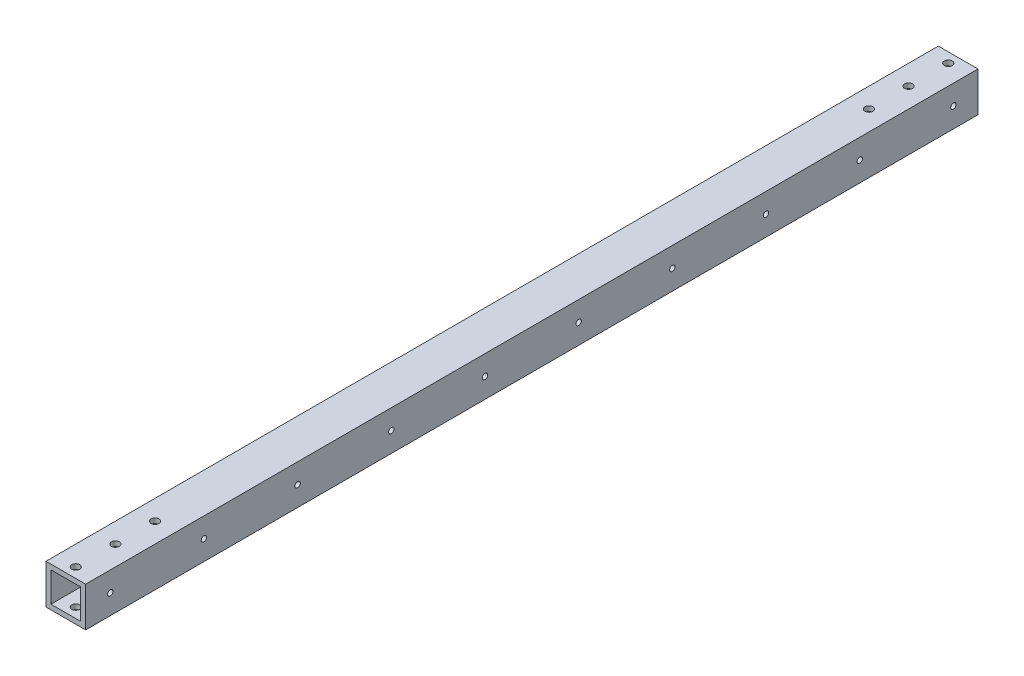
SolidWorks part; units mm, degrees
material "6061-T6 (SS)"
ref_plane "Front Plane" through (0, 0, 0) normal (0, 0, 1) x (1, 0, 0)
ref_plane "Top Plane" through (0, 0, 0) normal (0, 1, 0) x (1, 0, 0)
ref_plane "Right Plane" through (0, 0, 0) normal (1, 0, 0) x (0, 0, -1)
sketch "Sketch1" plane through (0, 0, 0) normal (0, 0, 1) x (1, 0, 0)
  line L1 (-12.7, -12.7) -> (12.7, -12.7)
  line L2 (-12.7, -12.7) -> (-12.7, 12.7)
  line L3 (-12.7, 12.7) -> (12.7, 12.7)
  line L4 (12.7, -12.7) -> (12.7, 12.7)
  line L5 (-12.7, -12.7) -> (12.7, 12.7) construction
  line L6 (-12.7, 12.7) -> (12.7, -12.7) construction
  point P0 (0, 0)
  dimension "D1" = 25.4
  dimension "D2" = 25.4
extrude "Extrude-Thin1" add sketch "Sketch1" along normal blind 571.5 thin thin type one direction reverse wall 3.175
hole_wizard "#10 Clearance Hole1" positions "3DSketch1" profile "Sketch3" hole size "#10" standard "ANSI Inch" end condition through all
sketch3d "3DSketch1"
  line L1 (12.7, 12.7, 0) -> (-12.7, 12.7, 0) construction
  line L6 (0, 12.7, 571.5) -> (0, 12.7, 0) construction
  line L7 (12.7, 12.7, 571.5) -> (-12.7, 12.7, 571.5) construction
  point P57 (0, 12.7, 6.35)
  point P59 (0, 12.7, 31.75)
  point P61 (0, 12.7, 57.15)
  point P63 (0, 12.7, 539.75)
  point P65 (0, 12.7, 514.35)
  point P67 (0, 12.7, 565.15)
  dimension "D1" = 25.4
  dimension "D2" = 25.4
  dimension "D3" = 6.35
  dimension "D4" = 25.4
  dimension "D5" = 25.4
  dimension "D6" = 6.35
sketch "Sketch3" plane through (0, 12.7, 565.15) normal (1, 0, 0) x (0, 0, 1)
  line L0 (0, 0) -> (0, 25.4)
  line L1 (0, 25.4) -> (2.5527, 25.4)
  line L2 (2.5527, 25.4) -> (2.5527, 0)
  line L5 (2.5527, 0) -> (0, 0)
  line L11 (0, -6.35) -> (0, 107.95) construction
  dimension "Thru Hole Dia." = 5.1054
  dimension "Thru Hole Depth" = 25.4
hole_wizard "#8-32 Tapped Hole1" positions "Sketch4" profile "Sketch5" tap size "#8-32" standard "ANSI Inch"
sketch "Sketch4" plane through (12.7, 82.55, 285.75) normal (1, 0, 0) x (0, 0, 1)
  point P0 (-270, 82.55)
  point P3 (-210, 82.55)
  point P6 (-150, 82.55)
  point P9 (-30, 82.55)
  point P12 (30, 82.55)
  point P15 (90, 82.55)
  point P18 (150, 82.55)
  point P21 (210, 82.55)
  point P24 (270, 82.55)
  point P27 (-90, 82.55)
sketch "Sketch5" plane through (12.7, 0, 15.75) normal (0, 1, 0) x (0, 0, -1)
  line L0 (0, 0) -> (0, 11.7464)
  line L1 (0, 11.7464) -> (1.7272, 10.7086)
  line L2 (1.7272, 10.7086) -> (1.7272, 0)
  line L3 (1.7272, 0) -> (0, 0)
  line L4 (0, 11.7464) -> (-1.7272, 10.7086) construction
  line L5 (0, -6.35) -> (0, 107.95) construction
  dimension "Tap Drill Dia." = 3.4544
  dimension "Tap Drill Depth" = 10.7086
  dimension "Drill Angle" = 118
